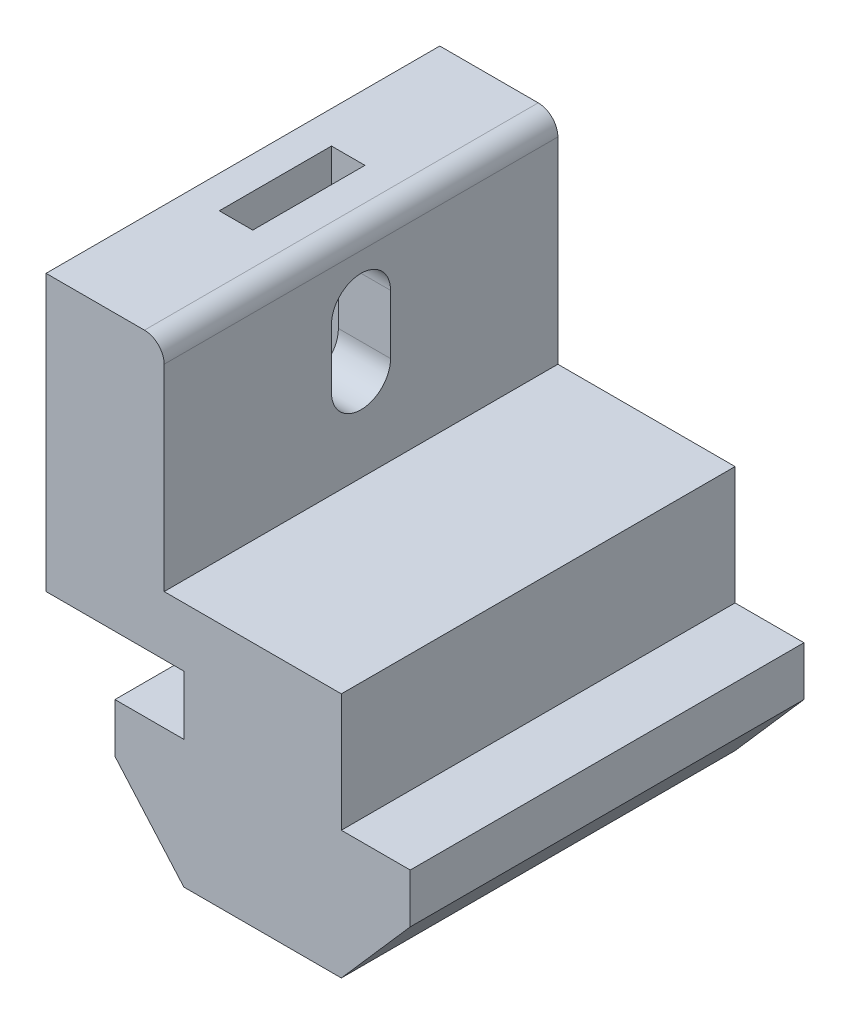
SolidWorks part; units mm, degrees
ref_plane "Piano frontale" through (0, 0, 0) normal (0, 0, 1) x (1, 0, 0)
ref_plane "Piano superiore" through (0, 0, 0) normal (0, 1, 0) x (1, 0, 0)
ref_plane "Piano destro" through (0, 0, 0) normal (1, 0, 0) x (0, 0, -1)
sketch "Schizzo2" plane through (0, 0, 0) normal (0, 0, 1) x (1, 0, 0)
  line L0 (0, 0) -> (0, 12.9875) construction
  line L1 (-4, 9.5) -> (-11, 9.5)
  line L2 (-11, 9.5) -> (-11, 23.5)
  line L3 (-11, 23.5) -> (-6, 23.5)
  line L4 (-5, 22.5) -> (-5, 12.5)
  line L5 (-5, 12.5) -> (4, 12.5)
  line L6 (4, 12.5) -> (4, 9.5)
  line L13 (-4, 0) -> (4, 0)
  line L14 (-7.5, 4) -> (-4, 0)
  line L15 (-7.5, 6.5) -> (-7.5, 4)
  line L16 (-4, 6.5) -> (-7.5, 6.5)
  line L17 (-4, 9.5) -> (-4, 6.5)
  line L44 (7.5, 4) -> (4, 0)
  line L45 (7.5, 6.5) -> (7.5, 4)
  line L46 (4, 6.5) -> (7.5, 6.5)
  line L72 (4, 9.5) -> (4, 6.5)
  arc A0 (-6, 23.5) -> (-5, 22.5) centre (-6, 22.5) cw
  point P9 (-5, 23.5)
  dimension "D11" = 1
  dimension "D1" = 8
  dimension "D2" = 4
  dimension "D3" = 2.5
  dimension "D4" = 8
  dimension "D5" = 3
  dimension "D6" = 15
  dimension "D7" = 11
  dimension "D8" = 6
  dimension "D9" = 3
  dimension "D10" = 14
extrude "Estrusione-Estrusione1" add sketch "Schizzo2" against normal blind 20
sketch "Schizzo6" plane through (-11, 0, 0) normal (-1, 0, 0) x (0, 0, 1)
  line L0 (0, 23.5) -> (0, 9.5) construction
  line L1 (-20, 23.5) -> (0, 23.5) construction
  line L2 (-10, 20) -> (-10, 17) construction
  line L3 (-8.5, 20) -> (-8.5, 17)
  line L4 (-11.5, 20) -> (-11.5, 17)
  line L5 (-20, 9.5) -> (0, 9.5) construction
  arc A1 (-8.5, 20) -> (-11.5, 20) centre (-10, 20) ccw
  arc A2 (-11.5, 17) -> (-8.5, 17) centre (-10, 17) ccw
  point P6 (-10, 18.5)
  dimension "D2" = 1.5
  dimension "D1" = 10
  dimension "D3" = 3.5
  dimension "D4" = 3
  dimension "D5" = 9
extrude "Taglio-Estrusione1" cut sketch "Schizzo6" against normal up to next
sketch "Schizzo11" plane through (0, 0, -20) normal (0, 0, -1) x (-1, 0, 0)
  line L0 (4, 0) -> (-4, 0) construction
  line L1 (7.5, 6.5) -> (7.5, 4) construction
  text T0 "3" font "Century Gothic" height 6.5
  dimension "D1" = 1
  dimension "D2" = 10.5
extrude "Estrusione-Estrusione4" add sketch "Schizzo11" along normal blind 0.6
sketch "Schizzo12" plane through (0, 23.5, 0) normal (0, 1, 0) x (1, 0, 0)
  line L0 (-6, 10) -> (-11, 10) construction
  line L1 (-6, 20) -> (-6, 0) construction
  line L2 (-11, 20) -> (-11, 0) construction
  line L4 (-7.65, 7.15) -> (-9.35, 7.15)
  line L5 (-7.65, 7.15) -> (-7.65, 12.85)
  line L6 (-7.65, 12.85) -> (-9.35, 12.85)
  line L7 (-9.35, 7.15) -> (-9.35, 12.85)
  line L8 (-7.65, 7.15) -> (-9.35, 12.85) construction
  line L9 (-7.65, 12.85) -> (-9.35, 7.15) construction
  point P6 (-8.5, 10)
  dimension "D1" = 1.7
  dimension "D2" = 5.7
extrude "Taglio-Estrusione2" cut sketch "Schizzo12" against normal blind 11
